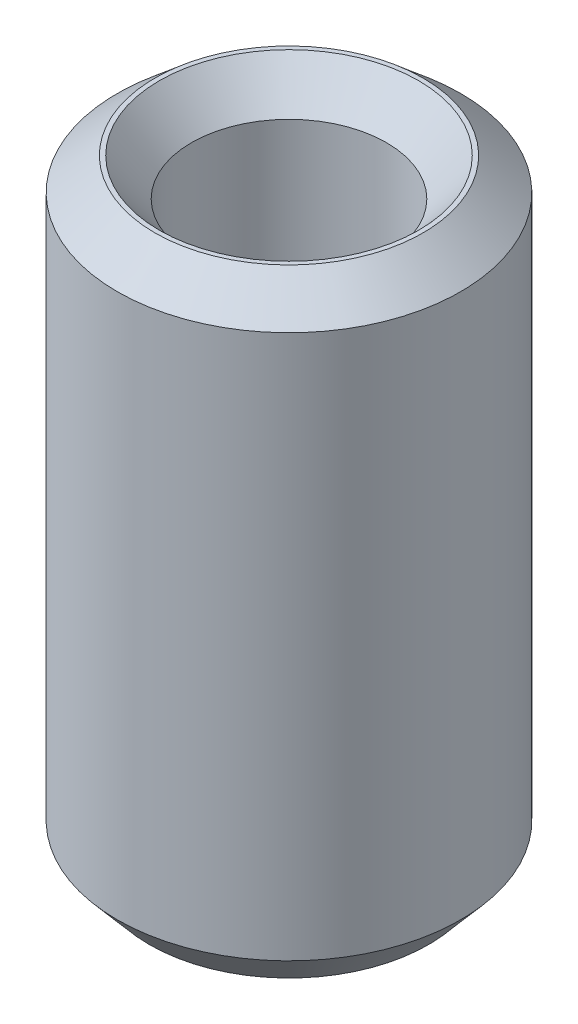
SolidWorks part; units mm, degrees
ref_plane "Front Plane" through (0, 0, 0) normal (0, 0, 1) x (1, 0, 0)
ref_plane "Top Plane" through (0, 0, 0) normal (0, 1, 0) x (1, 0, 0)
ref_plane "Right Plane" through (0, 0, 0) normal (1, 0, 0) x (0, 0, -1)
sketch "Sketch1" plane through (0, 0, 0) normal (0, 1, 0) x (1, 0, 0)
  circle A0 centre (0, 0) radius 15
  dimension "SLEEVE_OD" = 30
extrude "Boss-Extrude1" add sketch "Sketch1" along normal blind 53.6103
sketch "Sketch2" plane through (0, 0, 0) normal (0, 1, 0) x (1, 0, 0)
  circle A0 centre (0, 0) radius 8.5154
  dimension "BORE_D" = 17.0308
extrude "Cut-Extrude1" cut sketch "Sketch2" along normal through all
chamfer "Chamfer1" distance 2.8061 angle 49.494 4 edges at (0, 53.6103, 8.5154) (0, 0, 8.5154) (0, 0, 15) (0, 53.6103, 15) first distance on face at (0, 53.6103, 8.5154) first distance on face at (0, 0, 8.5154) first distance on face at (0, 53.6103, 15)
